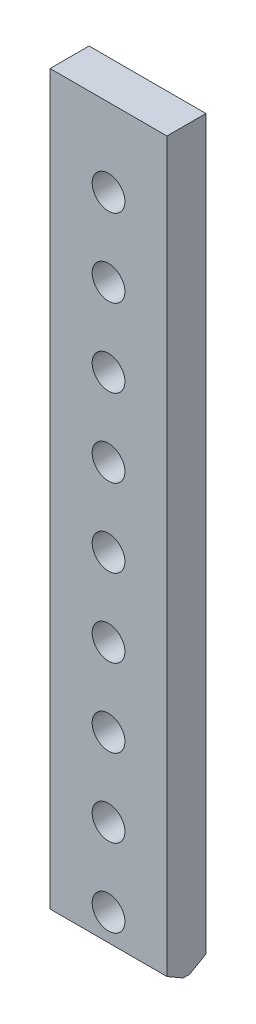
SolidWorks part; units mm, degrees
ref_plane "Спереди" through (0, 0, 0) normal (0, 0, 1) x (1, 0, 0)
ref_plane "Сверху" through (0, 0, 0) normal (0, 1, 0) x (1, 0, 0)
ref_plane "Справа" through (0, 0, 0) normal (1, 0, 0) x (0, 0, -1)
sketch "Эскиз1" plane through (0, 0, 0) normal (0, 0, 1) x (1, 0, 0)
  line L1 (0, 0) -> (75, 0)
  line L2 (0, 0) -> (0, 473)
  line L3 (0, 473) -> (75, 473)
  line L4 (75, 0) -> (75, 473)
  point P5 (37.5, 473)
  dimension "D1" = 473
  dimension "D2" = 75
extrude "Бобышка-Вытянуть1" add sketch "Эскиз1" along normal blind 25
sketch "Эскиз2" plane through (0, 0, 25) normal (0, 0, 1) x (1, 0, 0)
  line L0 (0, 0) -> (75, 0) construction
  line L1 (75, 0) -> (75, 473) construction
  circle A0 centre (37.5, 23) radius 10.5
  circle A1 centre (37.5, 73) radius 10.5
  circle A2 centre (37.5, 123) radius 10.5
  circle A3 centre (37.5, 173) radius 10.5
  circle A4 centre (37.5, 223) radius 10.5
  circle A5 centre (37.5, 273) radius 10.5
  circle A6 centre (37.5, 323) radius 10.5
  circle A7 centre (37.5, 373) radius 10.5
  circle A8 centre (37.5, 423) radius 10.5
  dimension "D1" = 9
  dimension "D2" = 23
  dimension "D3" = 37.5
  dimension "D4" = 21
extrude "Вырез-Вытянуть1" cut sketch "Эскиз2" against normal through all
chamfer "Фаска1" distance 6 angle 60 1 edges at (37.5, 0, 0) first distance on face at (48, 73, 0)
chamfer "Фаска2" distance 6 angle 60 1 edges at (37.5, 0, 25) first distance on face at (48, 73, 25)
